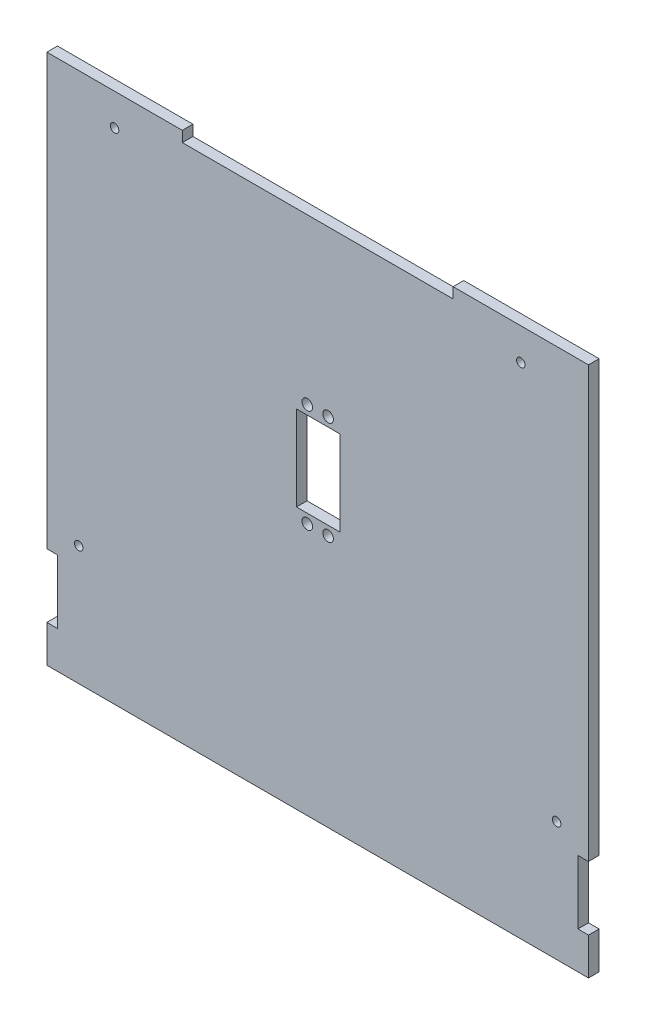
SolidWorks part; units mm, degrees
ref_plane "Front Plane" through (0, 0, 0) normal (0, 0, 1) x (1, 0, 0)
ref_plane "Top Plane" through (0, 0, 0) normal (0, 1, 0) x (1, 0, 0)
ref_plane "Right Plane" through (0, 0, 0) normal (1, 0, 0) x (0, 0, -1)
sketch "Sketch2" plane through (0, 0, 0) normal (0, 0, 1) x (1, 0, 0)
  line L1 (-130, 125) -> (125, 125)
  line L3 (-130, -125) -> (125, -125)
  line L6 (-130, 125) -> (-130, -125)
  line L8 (125, 125) -> (125, -125)
  point P8 (-2.5, -125)
extrude "Boss-Extrude1" add sketch "Sketch2" along normal blind 5
sketch "Sketch4" plane through (0, 0, 0) normal (0, 0, -1) x (-1, 0, 0)
  line L1 (-125, 125) -> (-7.5, 125)
  line L2 (-125, 125) -> (-125, 45.55)
  line L3 (-125, 45.55) -> (-7.5, 45.55)
  line L4 (-7.5, 125) -> (-7.5, 45.55)
  line L5 (-7.5, 45.55) -> (12.5, 45.55)
  line L6 (-7.5, 45.55) -> (-7.5, -8.95)
  line L7 (-7.5, -8.95) -> (12.5, -8.95)
  line L8 (12.5, 45.55) -> (12.5, -8.95)
extrude "Cut-Extrude1" cut sketch "Sketch4" against normal blind 23 and the other way blind 32 contours L8 L5 L6 L7 region at (-2.5, 18.3, 0)
sketch "Sketch5" plane through (0, 0, 0) normal (0, 0, -1) x (-1, 0, 0)
  line L0 (-7.5, 45.55) -> (-7.5, 38.3)
  line L1 (-7.5, 45.55) -> (-7.5, -8.95) construction
  line L2 (-7.5, 38.3) -> (12.5, 38.3)
  line L3 (12.5, 45.55) -> (12.5, -8.95) construction
  line L4 (12.5, 38.3) -> (12.5, 45.55)
  line L5 (12.5, 45.55) -> (-7.5, 45.55)
  line L6 (-7.5, -8.95) -> (-7.5, -1.7)
  line L7 (-7.5, -1.7) -> (12.5, -1.7)
  line L8 (12.5, -1.7) -> (12.5, -8.95)
  line L9 (12.5, -8.95) -> (-7.5, -8.95)
extrude "Boss-Extrude3" add sketch "Sketch5" against normal up to surface (5 mm away) up to face at (-2.5, 18.3, 5)
sketch "Sketch6" plane through (0, 0, 0) normal (0, 0, -1) x (-1, 0, 0)
  line L0 (-7.5, 38.3) -> (-7.5, 48.3)
  line L1 (-7.5, -1.7) -> (-7.5, -11.7)
  line L2 (-7.5, -11.7) -> (-32.5, -11.7)
  line L3 (-32.5, -11.7) -> (-32.5, 48.3)
  line L4 (-32.5, 48.3) -> (-7.5, 48.3)
  line L6 (-7.5, 38.3) -> (-7.5, -1.7)
extrude "Cut-Extrude2" cut sketch "Sketch6" against normal blind 23
sketch "Sketch7" plane through (0, 0, 0) normal (0, 0, -1) x (-1, 0, 0)
  circle A0 centre (-2.4, 42.6) radius 2.5
  circle A1 centre (7.4, 42.6) radius 2.5
  circle A2 centre (-2.4, -6) radius 2.5
  circle A3 centre (7.4, -6) radius 2.5
extrude "Cut-Extrude3" cut sketch "Sketch7" against normal blind 23
sketch "Sketch8" plane through (0, 0, 0) normal (0, 0, -1) x (-1, 0, 0)
  line L0 (-7.5, 38.3) -> (-7.5, 38.8)
  line L1 (-32.5, 48.3) -> (-7.5, 48.3)
  line L2 (-32.5, 48.3) -> (-32.5, -11.7)
  line L3 (-32.5, -11.7) -> (-7.5, -11.7)
  line L4 (-7.5, 48.3) -> (-7.5, -11.7)
  line L5 (-7.5, 38.8) -> (-8, 38.8)
  line L6 (12.5, -1.7) -> (13, -1.7)
  line L7 (13, -1.7) -> (13, -2.2)
  line L9 (-8, 38.8) -> (13, 38.8)
  line L10 (-8, 38.8) -> (-8, -2.2)
  line L11 (-8, -2.2) -> (13, -2.2)
  line L12 (13, 38.8) -> (13, -2.2)
  line M9 (-32.5, 48.3) -> (-7.5, 48.3)
  line M10 (-7.5, 48.3) -> (-7.5, 38.3)
  line M15 (-7.5, -11.7) -> (-32.5, -11.7)
  line M16 (-32.5, -11.7) -> (-32.5, 48.3)
extrude "Boss-Extrude6" add sketch "Sketch8" against normal up to surface (5 mm away) contours L11 L10 L5 L4 M10 M9 M16 M15 region at (20.1697, 18.3, 0) up to face at (-4.9, 42.6, 5)
sketch "Sketch9" plane through (0, 0, 0) normal (0, 0, -1) x (-1, 0, 0)
  line L1 (-8, 38.8) -> (-7.5, 38.8)
  line L2 (-8, 38.8) -> (-8, 38.3)
  line L3 (-8, 38.3) -> (-7.5, 38.3)
  line L4 (-7.5, 38.8) -> (-7.5, 38.3)
  line L5 (-7.5, -1.7) -> (-8, -1.7)
  line L6 (-7.5, -1.7) -> (-7.5, -2.2)
  line L7 (-7.5, -2.2) -> (-8, -2.2)
  line L8 (-8, -1.7) -> (-8, -2.2)
extrude "Boss-Extrude7" add sketch "Sketch9" against normal up to surface (5 mm away) up to face at (2.625, 18.3, 5)
sketch "Sketch10" plane through (0, 0, 0) normal (0, 0, -1) x (-1, 0, 0)
  line L0 (130, -125) -> (130, -60)
  line L1 (130, 125) -> (130, -125) construction
  line L2 (130, -60) -> (136, -60)
  line L3 (136, -60) -> (136, -125)
  line L4 (136, -125) -> (130, -125)
  line L5 (130, -125) -> (130, -107.5)
  line L6 (130, -107.5) -> (130, -77.5)
  line L7 (130, -77.5) -> (125, -77.5)
  line L8 (125, -77.5) -> (125, -107.5)
  line L9 (125, -107.5) -> (130, -107.5)
  line L10 (2.5, 125) -> (2.5, 50.8833)
  line L11 (-125, 125) -> (130, 125) construction
  line L12 (-120, -107.5) -> (-125, -107.5)
  line L13 (-120, -77.5) -> (-120, -107.5)
  line L14 (-125, -77.5) -> (-120, -77.5)
  line L15 (-125, -107.5) -> (-125, -77.5)
  line L16 (-125, -125) -> (-125, -107.5)
  line L17 (-131, -125) -> (-125, -125)
  line L18 (-131, -60) -> (-131, -125)
  line L19 (-125, -60) -> (-131, -60)
  line L20 (-125, -125) -> (-125, -60)
  line M11 (130, -125) -> (130, 125)
extrude "Boss-Extrude8" add sketch "Sketch10" against normal up to surface (5 mm away) contours L4 L3 L2 L0 M11 | L20 L19 L18 L17 region at (-133, -92.5, 0) up to face at (-2.25, 18.3, 5)
extrude "Cut-Extrude4" cut sketch "Sketch10<3>" against normal blind 10 contours L8 L9 L0 L7 | L15 L14 L13 L12 region at (-127.5, -92.5, 0)
sketch "Sketch10<3>" plane through (0, 0, 0) normal (0, 0, -1) x (-1, 0, 0) same geometry as "Sketch10"
sketch "Sketch11" plane through (0, 0, 0) normal (0, 0, -1) x (-1, 0, 0)
  line L1 (-131, -60) -> (-125, -60)
  line L2 (-131, -60) -> (-131, 125)
  line L3 (-131, 125) -> (-125, 125)
  line L4 (-125, -60) -> (-125, 125)
  line L5 (130, 125) -> (136, 125)
  line L6 (130, 125) -> (130, -60)
  line L7 (130, -60) -> (136, -60)
  line L8 (136, 125) -> (136, -60)
extrude "Boss-Extrude9" add sketch "Sketch11" against normal up to surface (5 mm away) up to face at (-127.5, -92.5, 5)
sketch "Sketch14" plane through (0, 0, 0) normal (0, 0, -1) x (-1, 0, 0)
  line L0 (136, -125) -> (-131, -125) construction
  line L1 (-125, -125) -> (-131, -125)
  line L2 (-125, -125) -> (-125, 125)
  line L3 (-125, 125) -> (-131, 125)
  line L4 (-131, -125) -> (-131, 125)
  line L6 (130, -125) -> (136, -125)
  line L7 (130, -125) -> (130, 125)
  line L8 (130, 125) -> (136, 125)
  line L9 (136, -125) -> (136, 125)
extrude "Cut-Extrude5" cut sketch "Sketch14" against normal blind 10
sketch "Sketch15" plane through (0, 0, 0) normal (0, 0, -1) x (-1, 0, 0)
  line L0 (-125, 125) -> (130, 125) construction
  line L1 (2.5, 125) -> (-61.25, 125)
  line L3 (2.5, 120) -> (-61.25, 120)
  line L7 (2.5, 125) -> (66.25, 125)
  line L9 (2.5, 120) -> (66.25, 120)
  line L11 (-61.25, 125) -> (-61.25, 120)
  line L12 (66.25, 120) -> (66.25, 125)
extrude "Cut-Extrude6" cut sketch "Sketch15" against normal blind 185
sketch "Sketch16" plane through (0, 0, 0) normal (0, 0, -1) x (-1, 0, 0)
  line L0 (-93.125, 125) -> (-93.125, 110)
  line L1 (-125, 125) -> (-61.25, 125) construction
  line L2 (2.5, 120) -> (2.5, 101.4878)
  line L3 (-61.25, 120) -> (66.25, 120) construction
  circle A0 centre (-93.125, 110) radius 1.5
  circle A1 centre (98.125, 110) radius 1.5
extrude "Cut-Extrude7" cut sketch "Sketch16" against normal blind 185 contours A0 | A1 region at (94.1557, 108.9693, 0) region at (-98.125, 110, 0)
sketch "Sketch17" plane through (0, 0, 0) normal (0, 0, -1) x (-1, 0, 0)
  line L0 (-125, -77.5) -> (-125, -60)
  line L1 (-125, -77.5) -> (-125, 125) construction
  line L2 (-125, -68.75) -> (-110, -68.75)
  line L3 (2.5, -125) -> (2.5, -56.9061)
  line L4 (130, -125) -> (-125, -125) construction
  circle A0 centre (-110, -68.75) radius 1.5
  circle A1 centre (115, -68.75) radius 1.5
extrude "Cut-Extrude8" cut sketch "Sketch17" against normal blind 185 contours A0 | A1 region at (110, -70.2076, 0) region at (-115, -68.75, 0)
sketch "Sketch18" plane through (0, 0, 0) normal (0, 0, -1) x (-1, 0, 0)
  circle A0 centre (-93.125, 110) radius 2
  circle A1 centre (98.125, 110) radius 2
  circle A2 centre (115, -68.75) radius 2
  circle A3 centre (-110, -68.75) radius 2
extrude "Cut-Extrude9" cut sketch "Sketch18" against normal blind 10
